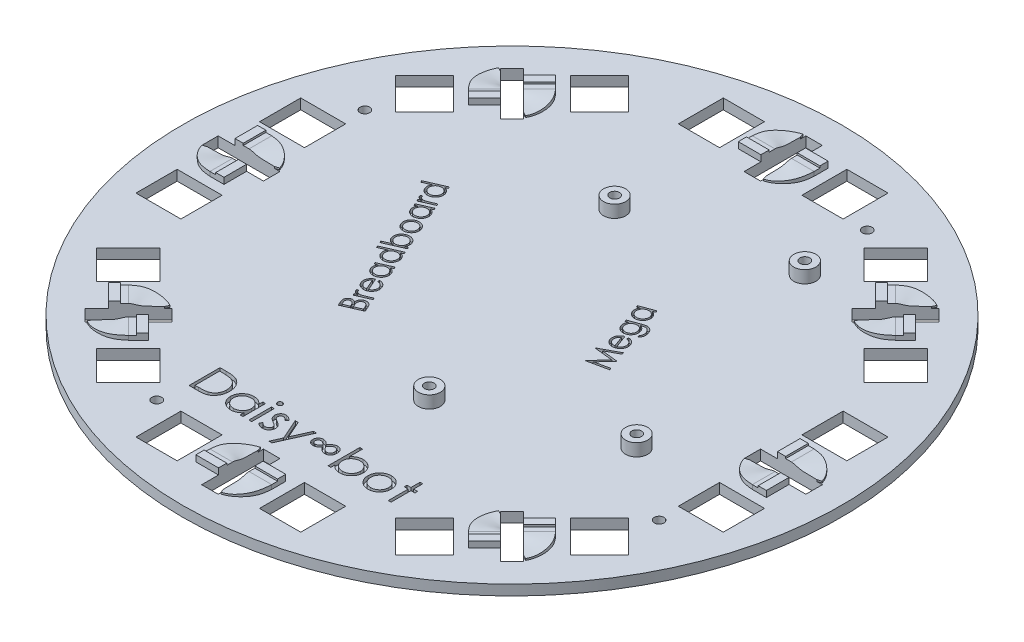
SolidWorks part; units mm, degrees
ref_plane "Front" through (0, 0, 0) normal (0, 0, 1) x (1, 0, 0)
ref_plane "Top" through (0, 0, 0) normal (0, 1, 0) x (1, 0, 0)
ref_plane "Right" through (0, 0, 0) normal (1, 0, 0) x (0, 0, -1)
sketch "Sketch1" plane through (0, 0, 0) normal (0, 1, 0) x (1, 0, 0)
  circle A0 centre (0, 0) radius 101.6
  dimension "D1" = 203.2
extrude "Base" add sketch "Sketch1" along normal blind 3.175 contours A0
sketch "Sketch2" plane through (0, 3.175, 0) normal (0, 1, 0) x (1, 0, 0)
  line L1 (-2.54, -93.1333) -> (2.54, -93.1333)
  line L2 (-2.54, -93.1333) -> (-2.54, -74.0833)
  line L3 (-2.54, -74.0833) -> (2.54, -74.0833)
  line L4 (2.54, -93.1333) -> (2.54, -74.0833)
  point P4 (0, -74.0833)
  dimension "D1" = 5.08
  dimension "D2" = 19.05
  dimension "D3" = 93.1333
extrude "Cut-Extrude1" cut sketch "Sketch2" against normal up to next and the other way through all contours L1 L4 L3 L2
sketch "Sketch4" plane through (0, 3.175, 0) normal (0, 1, 0) x (1, 0, 0)
  line L0 (0, -83.6083) -> (-2.9434, -74.5495) construction
  line L1 (-2.9434, -74.5495) -> (0, -83.6083) construction
  line L2 (0, -83.6083) -> (-5.5987, -75.9024) construction
  line L3 (0, -83.6083) -> (-7.7059, -78.0097) construction
  line L4 (0, -83.6083) -> (-9.0588, -80.6649) construction
  line L5 (0, -83.6083) -> (-9.525, -83.6083) construction
  line L9 (2.54, -74.0833) -> (-2.54, -74.0833) construction
  line L10 (2.54, -74.0833) -> (2.54, -93.1333) construction
  line L11 (-2.54, -74.0833) -> (-2.54, -93.1333) construction
  line L12 (2.54, -93.1333) -> (-2.54, -93.1333) construction
  circle A0 centre (0, -83.6083) radius 9.525 construction
  point P16 (0, -74.0833)
  point P19 (2.54, -83.6083)
  dimension "D1" = 18
  dimension "D2" = 18
  dimension "D3" = 18
  dimension "D4" = 18
  dimension "D5" = 18
ref_plane "Plane1" through (-24.5719, 0, 7.9839) normal (0.9511, 0, -0.309) x (-0.309, 0, -0.9511)
ref_plane "Plane2" through (-39.7581, 0, 28.886) normal (0.809, 0, -0.5878) x (-0.5878, 0, -0.809)
ref_plane "Plane3" through (-39.7581, 0, 54.7224) normal (0.5878, 0, -0.809) x (-0.809, 0, -0.5878)
ref_plane "Plane4" through (-24.5719, 0, 75.6244) normal (0.309, 0, -0.9511) x (-0.9511, 0, -0.309)
ref_plane "Plane5" through (0, 0, 83.6083) normal (0, 0, -1) x (-1, 0, 0)
sketch "Sketch5" plane through (-24.5719, 0, 7.9839) normal (0.9511, 0, -0.309) x (-0.309, 0, -0.9511)
  line L0 (-69.6725, 3.175) -> (-87.7902, 3.175) construction
  line L1 (-71.2966, 3.175) -> (-69.9913, 3.175)
  line L2 (-71.2966, 3.175) -> (-71.2966, 3.683)
  line L3 (-71.2966, 3.683) -> (-69.9913, 3.683)
  line L4 (-69.9913, 3.175) -> (-69.9913, 3.683)
  dimension "D2" = 0.508
sketch "Sketch6" plane through (-39.7581, 0, 28.886) normal (0.809, 0, -0.5878) x (-0.5878, 0, -0.809)
  line L0 (-58.4417, 3.175) -> (-73.8535, 3.175) construction
  line L1 (-63.3193, 3.175) -> (-58.1156, 3.175)
  line L2 (-63.3193, 3.175) -> (-63.3193, 3.775)
  line L3 (-63.3193, 3.775) -> (-58.1156, 3.775)
  line L4 (-58.1156, 3.175) -> (-58.1156, 3.775)
  dimension "D2" = 0.6
sketch "Sketch7" plane through (-39.7581, 0, 54.7224) normal (0.5878, 0, -0.809) x (-0.809, 0, -0.5878)
  line L0 (-41.4902, 3.175) -> (-52.6875, 3.175) construction
  line L1 (-46.0041, 3.175) -> (-39.6187, 3.175)
  line L2 (-46.0041, 3.175) -> (-46.0041, 4.075)
  line L3 (-46.0041, 4.075) -> (-39.6187, 4.075)
  line L4 (-39.6187, 3.175) -> (-39.6187, 4.075)
  dimension "D2" = 0.9
sketch "Sketch10" plane through (-24.5719, 0, 75.6244) normal (0.309, 0, -0.9511) x (-0.9511, 0, -0.309)
  line L0 (-25.8364, 3.175) -> (-16.7776, 3.175) construction
  line L1 (-23.1657, 3.175) -> (-16.3114, 3.175)
  line L2 (-23.1657, 3.175) -> (-23.1657, 4.375)
  line L3 (-23.1657, 4.375) -> (-16.3114, 4.375)
  line L4 (-16.3114, 3.175) -> (-16.3114, 4.375)
  dimension "D3" = 1.2
sketch "Sketch11" plane through (0, 0, 83.6083) normal (0, 0, -1) x (-1, 0, 0)
  line L0 (0, 3.175) -> (9.525, 3.175) construction
  line L1 (2.54, 3.175) -> (9.525, 3.175)
  line L2 (2.54, 3.175) -> (2.54, 4.475)
  line L3 (2.54, 4.475) -> (9.525, 4.475)
  line L4 (9.525, 3.175) -> (9.525, 4.475)
  dimension "D3" = 1.3
loft "Loft1" add profiles "Sketch5", "Sketch6", "Sketch7", "Sketch10", "Sketch11" connector at (-2.54, 3.683, 75.791) connector at (-2.54, 3.775, 80.1123) connector at (-2.54, 4.075, 81.7629) connector at (-2.54, 4.375, 82.783) connector at (-2.54, 4.475, 83.6083)
sketch "Sketch13" plane through (-104.9799, 0, 83.6083) normal (0, 0, -1) x (-1, 0, 0)
  line L6 (-95.4549, 3.175) -> (-102.4399, 3.175)
  line L7 (-95.4549, 3.175) -> (-95.4549, 4.475)
  line L8 (-95.4549, 4.475) -> (-102.4399, 4.475)
  line L9 (-102.4399, 3.175) -> (-102.4399, 4.475)
extrude "Boss-Extrude4" add sketch "Sketch13" against normal blind 1.7907
sketch "Sketch25" plane through (0, 0, 85.399) normal (0, 0, 1) x (1, 0, 0)
  line L0 (-9.525, 4.475) -> (-2.54, 4.475) construction
  line L1 (-9.525, 3.175) -> (-2.54, 3.175)
  line L2 (-9.525, 3.175) -> (-9.525, 5.075)
  line L3 (-9.525, 5.075) -> (-2.54, 5.075)
  line L4 (-2.54, 3.175) -> (-2.54, 5.075)
  dimension "D1" = 0.6
extrude "Boss-Extrude5" add sketch "Sketch25" along normal blind 2.54
sketch "Sketch14" plane through (-2.54, 0, 0) normal (1, 0, 0) x (0, 0, -1)
  line L0 (-83.6083, 3.175) -> (-83.6083, 0) construction
  line L1 (-74.0833, 0) -> (-93.1333, 0) construction
ref_plane "Plane6" through (0, 0, 0) normal (1, 0, 0) x (0, 0, -1)
sketch "Sketch15" plane through (0, 0, 0) normal (1, 0, 0) x (0, 0, -1)
  line L0 (-83.6083, 0) -> (-83.6083, 3.175) construction
pattern_circular "CirPattern1" count 2 over 360 about axis through (0, 0, 83.6083) along (0, 1, 0) of "Loft1", "Boss-Extrude5", "Boss-Extrude4" reverse direction yes
ref_axis "Axis1" through (0, 50, 0) along (0, -1, 0)
pattern_circular "CirPattern5" count 8 over 360 about axis through (0, 50, 0) along (0, -1, 0) of "CirPattern1", "Cut-Extrude1"
sketch "Sketch18" plane through (0, 3.175, 0) normal (0, 1, 0) x (1, 0, 0)
  line L0 (-12.3739, 44.0137) -> (34.085, 57.075) construction
  line L1 (-12.3739, 44.0137) -> (9.9679, -35.4555) construction
  line L2 (34.085, 57.075) -> (34.4287, 55.8524) construction
  line L3 (54.7082, -16.2811) -> (8.2493, -29.3425) construction
  line L4 (0, -101.6) -> (0, 101.6) construction
  line L5 (0, -1.7463) -> (0, 1.7463) construction
  line L6 (-101.6, 0) -> (101.6, 0) construction
  line L7 (34.4287, 55.8524) -> (54.7082, -16.2811) construction
  circle A0 centre (-12.3739, 44.0137) radius 3.405
  circle A1 centre (9.9679, -35.4555) radius 3.405
  circle A2 centre (54.7082, -16.2811) radius 3.405
  circle A3 centre (34.4287, 55.8524) radius 3.405
  circle A4 centre (9.9679, -35.4555) radius 1.5
  circle A5 centre (-12.3739, 44.0137) radius 1.5
  circle A6 centre (34.4287, 55.8524) radius 1.5
  circle A7 centre (54.7082, -16.2811) radius 1.5
  circle A8 centre (0, 0) radius 101.6 construction
  dimension "D7" = 1.905
  dimension "D8" = 3
  dimension "D9" = 1.27
  dimension "D1" = 82.55
  dimension "D2" = 74.93
  dimension "D4" = 15.703
  dimension "D5" = 36.83
  dimension "D10" = 48.26
sketch "Sketch19" plane through (0, 3.175, 0) normal (0, 1, 0) x (1, 0, 0)
  line L0 (-32.0765, -77.4396) -> (0, 0) construction
  line L1 (0, -101.6) -> (0, 101.6) construction
  circle A1 centre (-32.0765, -77.4396) radius 1.5
  circle A4 centre (0, 0) radius 101.6 construction
  dimension "D4" = 3
  dimension "D6" = 83.82
  dimension "D5" = 22.5
extrude "Cut-Extrude2" cut sketch "Sketch19" against normal through all
pattern_circular "CirPattern7" count 4 over 360 about axis through (0, 50, 0) along (0, -1, 0) of "Cut-Extrude2"
extrude "Mega_Screws" add sketch "Sketch18" along normal blind 3.81
sketch "Sketch23" plane through (0, 3.175, 0) normal (0, 1, 0) x (1, 0, 0)
  line L9 (-2.54, -87.939) -> (-2.54, -93.1333) construction
  line L10 (-25.4, -76.6805) -> (-12.7, -76.6805)
  line L11 (-25.4, -76.6805) -> (-25.4, -90.5362)
  line L16 (-25.4, -90.5362) -> (-12.7, -90.5362)
  line L17 (-12.7, -76.6805) -> (-12.7, -90.5362)
  line L19 (2.54, -74.0833) -> (2.54, -79.2776) construction
  line L20 (0, -50) -> (0, 50) construction
  line L21 (12.7, -76.6805) -> (12.7, -90.5362)
  line L22 (25.4, -90.5362) -> (12.7, -90.5362)
  line L23 (25.4, -76.6805) -> (25.4, -90.5362)
  line L24 (25.4, -76.6805) -> (12.7, -76.6805)
  point P8 (-2.54, -90.5362)
  point P9 (2.54, -76.6805)
  dimension "D1" = 12.7
  dimension "D2" = 10.16
extrude "Cut-Extrude6" cut sketch "Sketch23" against normal through all
pattern_circular "CirPattern8" count 8 over 360 about axis through (0, 50, 0) along (0, -1, 0) of "Cut-Extrude6"
sketch "Sketch17" plane through (0, 3.175, 0) normal (0, 1, 0) x (1, 0, 0)
  line L0 (33.02, -68.58) -> (-33.02, -68.58) construction
  line L1 (2.54, -74.0833) -> (-2.54, -74.0833) construction
  point P3 (0, -68.58)
  point P7 (0, -74.0833)
  dimension "D2" = 68.58
  dimension "D1" = 66.04
sketch "Sketch16" plane through (0, 3.175, 0) normal (0, 1, 0) x (1, 0, 0)
  line L0 (33.02, -68.58) -> (-33.02, -68.58) construction
  text T0 "Daisy∞bot\r\n" font "Century Gothic" height in points 36
extrude "Cut-Extrude4" cut sketch "Sketch16" against normal blind 1.27
sketch "Sketch22" plane through (0, 3.175, 0) normal (0, 1, 0) x (1, 0, 0)
  line L0 (-44.1287, 25.1735) -> (-20.5694, -28.6741) construction
  text T0 "Breadboard"
extrude "Cut-Extrude5" cut sketch "Sketch22" against normal blind 1.27
sketch "Sketch24" plane through (0, 3.175, 0) normal (0, 1, 0) x (1, 0, 0)
  line L0 (29.8571, 0) -> (21.0896, 23.8389) construction
  text T0 "Mega"
  dimension "D1" = 28.022
  dimension "D2" = 25.4
  dimension "D3" = 29.8571
extrude "Cut-Extrude7" cut sketch "Sketch24" against normal blind 1.27
